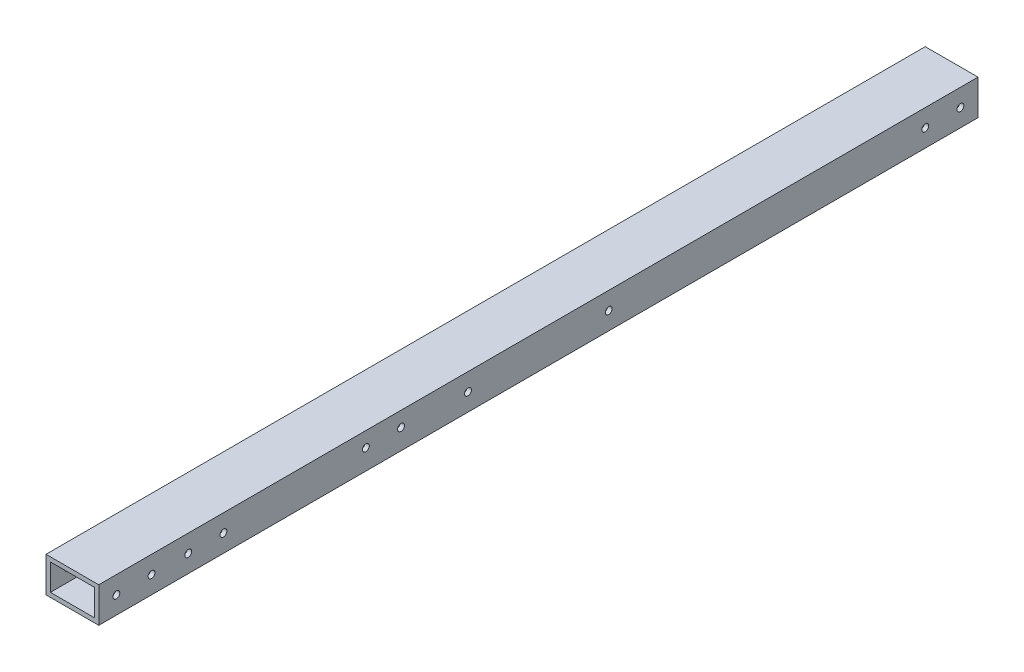
SolidWorks part; units mm, degrees
material "1060 Alloy"
ref_plane "Front Plane" through (0, 0, 0) normal (0, 0, 1) x (1, 0, 0)
ref_plane "Top Plane" through (0, 0, 0) normal (0, 1, 0) x (1, 0, 0)
ref_plane "Right Plane" through (0, 0, 0) normal (1, 0, 0) x (0, 0, -1)
sketch "Sketch1" plane through (0, 0, 0) normal (0, 0, 1) x (1, 0, 0)
  line L0 (-15.875, 9.525) -> (15.875, 9.525)
  line L2 (-19.05, 12.7) -> (19.05, 12.7)
  line L3 (-19.05, 12.7) -> (-19.05, -12.7)
  line L4 (-19.05, -12.7) -> (19.05, -12.7)
  line L5 (19.05, 12.7) -> (19.05, -12.7)
  line L10 (15.875, 9.525) -> (15.875, -9.525)
  line L11 (-15.875, -9.525) -> (15.875, -9.525)
  line L12 (-15.875, 9.525) -> (-15.875, -9.525)
  point P12 (0, 12.7)
  point P14 (19.05, 0)
  dimension "Wall Thickness" = 3.175
  dimension "Outside Width" = 38.1
  dimension "Outside Height" = 25.4
  dimension "Inside Height" = 19.05
  dimension "Inside Width" = 31.75
sketch "Sketch2" plane through (0, 0, 0) normal (1, 0, 0) x (0, 0, -1)
  line L0 (317.5, 0) -> (-317.5, 0)
  point P4 (0, 0)
  point P7 (-317.5, 0)
  point P10 (317.5, 0)
  dimension "Length" = 635
sketch "Sketch3" plane through (0, 0, 0) normal (0, 0, 1) x (1, 0, 0)
  line L21 (19.05, 12.7) -> (-19.05, 12.7)
  line L22 (19.05, -12.7) -> (19.05, 12.7)
  line L23 (-19.05, -12.7) -> (19.05, -12.7)
  line L24 (-19.05, 12.7) -> (-19.05, -12.7)
  line L25 (19.05, 12.7) -> (-19.05, 12.7)
  line L26 (19.05, -12.7) -> (19.05, 12.7)
  line L27 (-19.05, -12.7) -> (19.05, -12.7)
  line L28 (-19.05, 12.7) -> (-19.05, -12.7)
  line L29 (15.875, 9.525) -> (-15.875, 9.525)
  line L30 (15.875, -9.525) -> (15.875, 9.525)
  line L31 (-15.875, -9.525) -> (15.875, -9.525)
  line L32 (-15.875, 9.525) -> (-15.875, -9.525)
  line L33 (15.875, 9.525) -> (-15.875, 9.525)
  line L34 (15.875, -9.525) -> (15.875, 9.525)
  line L35 (-15.875, -9.525) -> (15.875, -9.525)
  line L36 (-15.875, 9.525) -> (-15.875, -9.525)
  dimension "D1" = 0
  dimension "D2" = 0
extrude "Boss-Extrude1" add sketch "Sketch3" along normal up to vertex (317.5 mm away) and the other way up to vertex (317.5 mm away) up to point (0, 0, 317.5) other way up to point (0, 0, -317.5)
sketch "Drawing Reference" plane through (0, 0, 0) normal (1, 0, 0) x (0, 0, -1)
  line L0 (-317.5, 0) -> (317.5, 0) construction
  line L1 (0, -12.7) -> (0, 12.7) construction
  line L2 (-317.5, -12.7) -> (317.5, -12.7) construction
  line L5 (-317.5, 12.7) -> (317.5, 12.7) construction
  point P7 (-290.068, 0)
  point P8 (290.068, 0)
  dimension "D1" = 27.432
sketch "Sketch4" plane through (-19.05, 0, 0) normal (-1, 0, 0) x (0, 0, 1)
  line L0 (-317.5, 0) -> (-304.8, 0)
  line L1 (-317.5, 12.7) -> (-317.5, -12.7) construction
  line L2 (-304.8, 0) -> (-279.4, 0)
  line L3 (317.5, 12.7) -> (317.5, -12.7) construction
  line L4 (317.5, 0) -> (304.8, 0)
  line L5 (304.8, 0) -> (279.4, 0)
  line L6 (0, 0) -> (50.8, 0) construction
  line L7 (0, 0) -> (-50.8, 0) construction
  point P11 (-304.8, 0)
  point P13 (-279.4, 0)
  point P14 (304.8, 0)
  point P15 (279.4, 0)
hole_wizard "#10 Clearance Hole2" positions "Sketch11" profile "Sketch12" hole size "#10" standard "ANSI Inch" end condition through all
sketch "Sketch11" plane through (-19.05, 0, 0) normal (-1, 0, 0) x (0, 0, 1)
  point P0 (-304.8, 0)
  point P3 (-279.4, 0)
  point P6 (279.4, 0)
  point P9 (304.8, 0)
sketch "Sketch12" plane through (-19.05, 0, -304.8) normal (0, 1, 0) x (0, 0, 1)
  line L0 (0, 0) -> (0, 38.1)
  line L1 (0, 38.1) -> (2.4892, 38.1)
  line L2 (2.4892, 38.1) -> (2.4892, 0)
  line L5 (2.4892, 0) -> (0, 0)
  line L11 (0, -6.35) -> (0, 107.95) construction
  dimension "Thru Hole Dia." = 4.9784
  dimension "Thru Hole Depth" = 38.1
hole_wizard "#10 Clearance Hole4" positions "Sketch14" profile "Sketch16" hole size "#10" standard "ANSI Inch" end condition through all
sketch "Sketch14" plane through (19.05, 0, 0) normal (1, 0, 0) x (0, 0, -1)
  point P33 (-252.857, 0)
  point P36 (-227.457, 0)
  point P42 (-124.587, 1.9434)
  point P45 (-99.187, 1.9434)
sketch "Sketch16" plane through (19.05, 0, 252.857) normal (0, 1, 0) x (0, 0, -1)
  line L0 (0, 0) -> (0, 38.1)
  line L1 (0, 38.1) -> (2.4892, 38.1)
  line L2 (2.4892, 38.1) -> (2.4892, 0)
  line L5 (2.4892, 0) -> (0, 0)
  line L11 (0, -6.35) -> (0, 107.95) construction
  dimension "Thru Hole Dia." = 4.9784
  dimension "Thru Hole Depth" = 38.1
hole_wizard "#10 Clearance Hole3" positions "Sketch20" profile "Sketch21" hole size "#10" standard "ANSI Inch" end condition through all
sketch "Sketch20" plane through (-19.05, 0, 0) normal (-1, 0, 0) x (0, 0, 1)
  point P0 (-50.8, 0)
  point P3 (50.8, 0)
sketch "Sketch21" plane through (-19.05, 0, -50.8) normal (0, 1, 0) x (0, 0, 1)
  line L0 (0, 0) -> (0, 38.1)
  line L1 (0, 38.1) -> (2.4892, 38.1)
  line L2 (2.4892, 38.1) -> (2.4892, 0)
  line L5 (2.4892, 0) -> (0, 0)
  line L11 (0, -6.35) -> (0, 107.95) construction
  dimension "Thru Hole Dia." = 4.9784
  dimension "Thru Hole Depth" = 38.1
equation "\"D1@Drawing Reference\"=\"Outside Width@Sketch1\" * 0.72"
